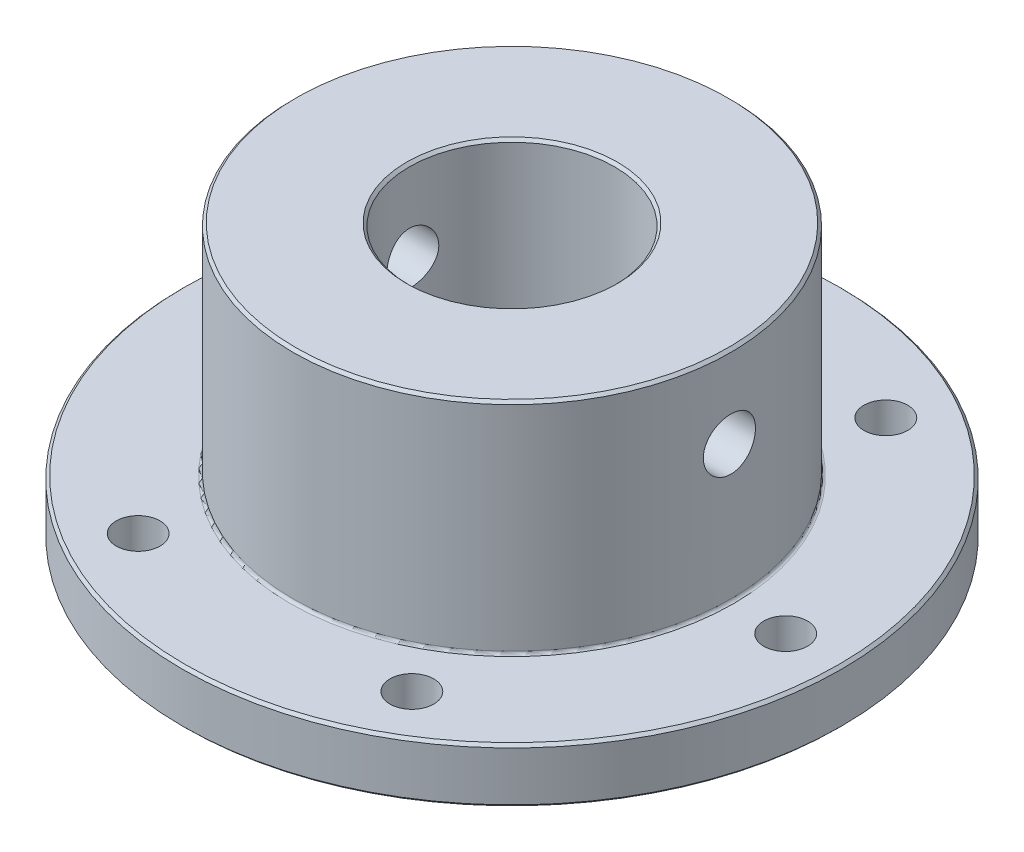
SolidWorks part; units mm, degrees
material "AISI 1020"
ref_plane "Alzado" through (0, 0, 0) normal (0, 0, 1) x (1, 0, 0)
ref_plane "Planta" through (0, 0, 0) normal (0, 1, 0) x (1, 0, 0)
ref_plane "Vista lateral" through (0, 0, 0) normal (1, 0, 0) x (0, 0, -1)
sketch "Croquis1" plane through (0, 0, 0) normal (0, 1, 0) x (1, 0, 0)
  line L0 (0, 0) -> (25, -43.3013) construction
  line L1 (50, 0) -> (25, 43.3013) construction
  line L2 (25, 43.3013) -> (-25, 43.3013) construction
  line L3 (-25, 43.3013) -> (-50, 0) construction
  line L4 (-50, 0) -> (-25, -43.3013) construction
  line L5 (-25, -43.3013) -> (25, -43.3013) construction
  line L6 (25, -43.3013) -> (50, 0) construction
  circle A0 centre (0, 0) radius 18.75
  circle A1 centre (0, 0) radius 60.2396
  circle A2 centre (0, 0) radius 43.3013 construction
  circle A3 centre (25, -43.3013) radius 4
  circle A4 centre (-25, -43.3013) radius 4
  circle A5 centre (-50, 0) radius 4
  circle A6 centre (-25, 43.3013) radius 4
  circle A7 centre (25, 43.3013) radius 4
  circle A8 centre (50, 0) radius 4
  dimension "D1" = 37.5
  dimension "D5" = 8
  dimension "D2" = 50
  dimension "D4" = 50
  dimension "D3" = 6
extrude "Saliente-Extruir1" add sketch "Croquis1" along normal blind 10
sketch "Croquis2" plane through (0, 10, 0) normal (0, 1, 0) x (1, 0, 0)
  circle A0 centre (0, 0) radius 18.75
  circle A1 centre (0, 0) radius 40
  dimension "D1" = 37.5
  dimension "D2" = 80
extrude "Saliente-Extruir2" add sketch "Croquis2" along normal blind 40
chamfer "Chaflán2" distance 0.5 angle 45 4 edges at (0, 10, 60.2396) (0, 0, 60.2396) (0, 50, 40) (0, 50, 18.75)
fillet "Redondeo1" radius 0.5 1 edges at (0, 10, 40)
sketch "Croquis3" plane through (0, 0, 0) normal (1, 0, 0) x (0, 0, -1)
  line L0 (0, 50) -> (0, 10) construction
  line L1 (19.25, 50) -> (-19.25, 50) construction
  line L2 (59.7396, 10) -> (-59.7396, 10) construction
  line L3 (39.5, 50) -> (-39.5, 50) construction
  circle A0 centre (0, 35) radius 4.7625
  dimension "D1" = 9.525
  dimension "D2" = 40
  dimension "D3" = 15
  dimension "D4" = 35
extrude "Cortar-Extruir1" cut sketch "Croquis3" against normal through all and the other way through all
